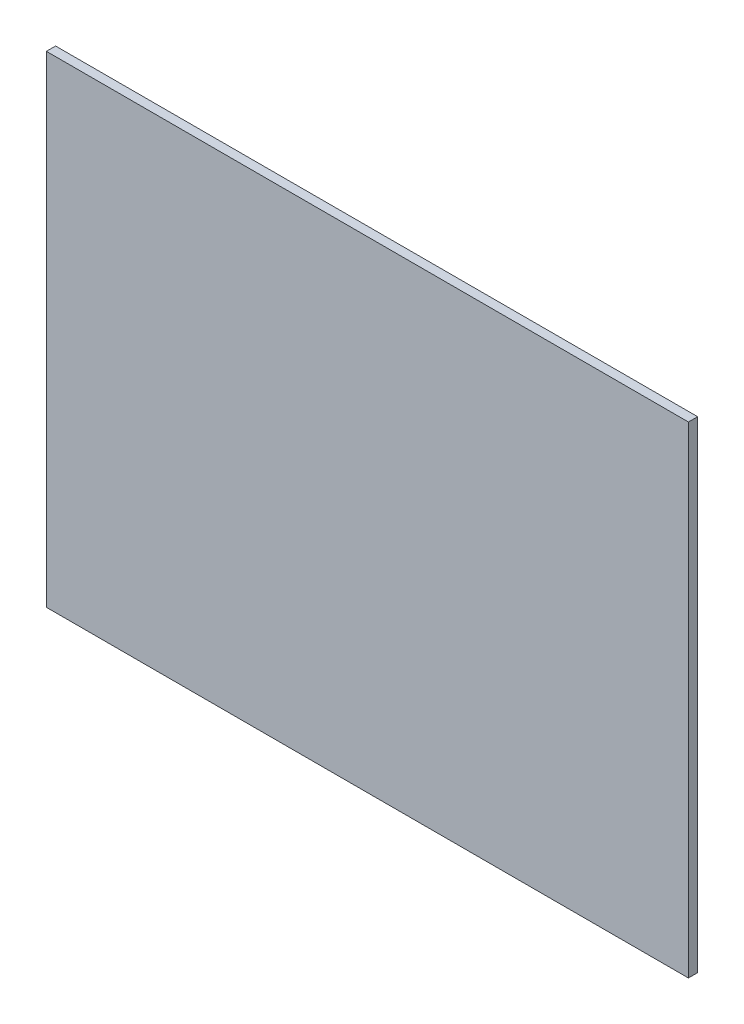
SolidWorks part; units mm, degrees
material "Cedar"
ref_plane "Front Plane" through (0, 0, 0) normal (0, 0, 1) x (1, 0, 0)
ref_plane "Top Plane" through (0, 0, 0) normal (0, 1, 0) x (1, 0, 0)
ref_plane "Right Plane" through (0, 0, 0) normal (1, 0, 0) x (0, 0, -1)
sketch "Sketch1" plane through (0, 0, 0) normal (0, 0, 1) x (1, 0, 0)
  line L1 (-609.6, -457.2) -> (609.6, -457.2)
  line L2 (-609.6, -457.2) -> (-609.6, 457.2)
  line L3 (-609.6, 457.2) -> (609.6, 457.2)
  line L4 (609.6, -457.2) -> (609.6, 457.2)
  line L5 (-609.6, -457.2) -> (609.6, 457.2) construction
  line L6 (-609.6, 457.2) -> (609.6, -457.2) construction
  point P0 (0, 0)
  dimension "D1" = 1219.2
  dimension "D2" = 914.4
extrude "Boss-Extrude1" add sketch "Sketch1" along normal blind 17.4752
